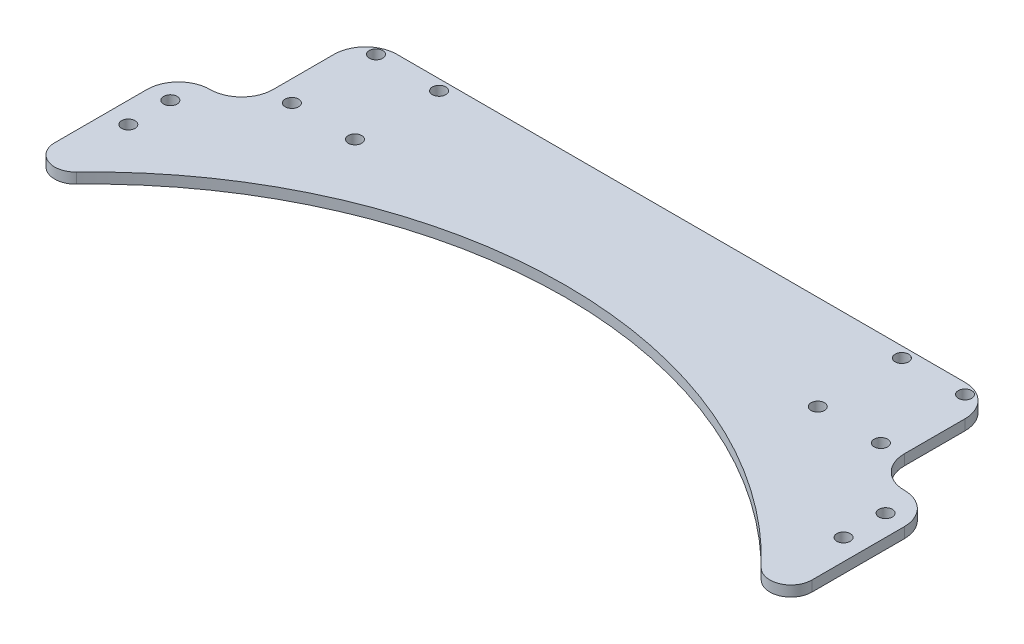
SolidWorks part; units mm, degrees
ref_plane "Front Plane" through (0, 0, 0) normal (0, 0, 1) x (1, 0, 0)
ref_plane "Top Plane" through (0, 0, 0) normal (0, 1, 0) x (1, 0, 0)
ref_plane "Right Plane" through (0, 0, 0) normal (1, 0, 0) x (0, 0, -1)
sketch "Sketch1" plane through (0, 0, 0) normal (0, 1, 0) x (1, 0, 0)
  line L0 (0, 0) -> (0, 92.075)
  line L1 (0, 92.075) -> (228.6, 92.075)
  line L2 (228.6, 92.075) -> (228.6, 0)
  arc A0 (0, 0) -> (228.6, 0) centre (114.3, -85.725) cw
  point P6 (0, 0)
  point P7 (0, 0)
  dimension "D3" = 142.875
  dimension "D1" = 177.8
  dimension "D2" = 228.6
extrude "Boss-Extrude1" add sketch "Sketch1" along normal blind 3.175
sketch "Sketch3" plane through (0, 0, 0) normal (0, -1, 0) x (1, 0, 0)
  line L0 (228.6, -92.075) -> (0, -92.075) construction
  line L1 (114.3, -92.075) -> (114.3, -57.15) construction
  circle A2 centre (44.45, -63.5) radius 2.032 construction
  circle A3 centre (25.4, -63.5) radius 2.032 construction
  arc A8 (0, 0) -> (228.6, 0) centre (114.3, 85.725) ccw construction
  circle A17 centre (44.45, -88.9) radius 2.032 construction
  circle A18 centre (25.4, -88.9) radius 2.032 construction
  circle A19 centre (44.45, -63.5) radius 2.032
  circle A20 centre (25.4, -63.5) radius 2.032
  circle A21 centre (44.45, -88.9) radius 2.032
  circle A22 centre (25.4, -88.9) radius 2.032
  circle A23 centre (203.2, -63.5) radius 2.032
  circle A24 centre (203.2, -88.9) radius 2.032
  circle A25 centre (184.15, -88.9) radius 2.032
  circle A26 centre (184.15, -63.5) radius 2.032
  point P12 (114.3, -92.075)
extrude "Cut-Extrude1" cut sketch "Sketch3" against normal through all
fillet "Fillet1" radius 6.35 2 edges at (0, 1.5875, 0) (228.6, 1.5875, 0)
sketch "Sketch4" plane through (0, 0, 0) normal (0, -1, 0) x (1, 0, 0)
  line L0 (0, -54.6893) -> (19.05, -54.6893)
  line L1 (0, -92.075) -> (0, -17.3036) construction
  line L15 (19.05, -54.6893) -> (19.05, -92.075)
  line L16 (19.05, -92.075) -> (0, -92.075)
  line L17 (0, -92.075) -> (0, -54.6893)
  line L18 (19.05, -57.9587) -> (19.05, -54.0361) construction
  line L19 (19.05, -57.9587) -> (19.05, -54.0361) construction
  line L20 (209.55, -57.9587) -> (209.55, -54.0361) construction
  line L21 (209.55, -57.9587) -> (209.55, -54.0361) construction
  line L22 (228.6, -92.075) -> (228.6, -54.6893)
  line L23 (228.6, -17.3036) -> (228.6, -92.075) construction
  line L24 (228.6, -54.6893) -> (209.55, -54.6893)
  line L25 (209.55, -54.6893) -> (209.55, -92.075)
  line L26 (228.6, -92.075) -> (0, -92.075) construction
  line L27 (209.55, -92.075) -> (228.6, -92.075)
  circle A0 centre (6.35, -33.1786) radius 2.032
  circle A1 centre (6.35, -45.8786) radius 2.032
  circle A3 centre (222.25, -33.1786) radius 2.032
  circle A4 centre (222.25, -45.8786) radius 2.032
  arc A6 (10.9436, -12.9194) -> (0, -17.3036) centre (6.35, -17.3036) ccw construction
  arc A7 (10.9436, -12.9194) -> (0, -17.3036) centre (6.35, -17.3036) ccw construction
  arc A8 (228.6, -17.3036) -> (217.6564, -12.9194) centre (222.25, -17.3036) ccw construction
  arc A9 (228.6, -17.3036) -> (217.6564, -12.9194) centre (222.25, -17.3036) ccw construction
  line M8 (0, -17.3036) -> (0, -92.075)
  line M9 (0, -92.075) -> (228.6, -92.075)
  line M10 (228.6, -92.075) -> (228.6, -17.3036)
  dimension "D2" = 4.064
  dimension "D1" = 12.7
  dimension "D3" = 15.875
extrude "Cut-Extrude2" cut sketch "Sketch4" against normal through all contours A0 | A1 | A3 | A4 | L15 L0 M8 M9 | L24 L25 M9 M10 region at (219.075, 0, -73.3822) region at (9.525, 0, -73.3822) region at (6.35, 0, -33.1786) region at (6.35, 0, -45.8786) region at (222.25, 0, -33.1786) region at (222.25, 0, -45.8786)
fillet "Fillet2" radius 9.525 6 edges at (209.55, 1.5875, -92.075) (209.55, 1.5875, -54.6893) (228.6, 1.5875, -54.6893) (19.05, 1.5875, -92.075) (19.05, 1.5875, -54.6893) (0, 1.5875, -54.6893)
